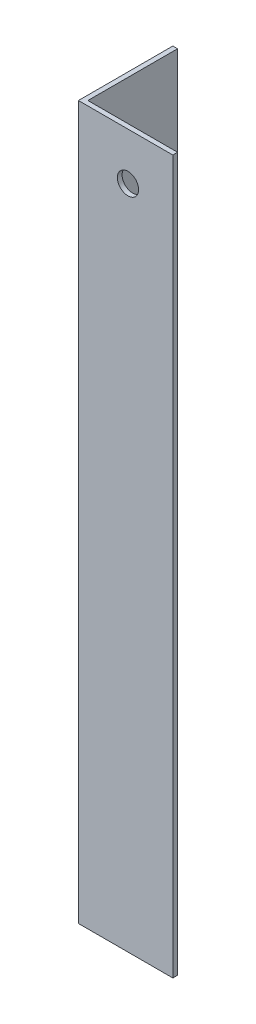
SolidWorks part; units mm, degrees
material "1060 Сплав"
ref_plane "Спереди" through (0, 0, 0) normal (0, 0, 1) x (1, 0, 0)
ref_plane "Сверху" through (0, 0, 0) normal (0, 1, 0) x (1, 0, 0)
ref_plane "Справа" through (0, 0, 0) normal (1, 0, 0) x (0, 0, -1)
sketch "Эскиз1" plane through (0, 0, 0) normal (0, 1, 0) x (1, 0, 0)
  line L0 (0, 0) -> (0, 20)
  line L1 (0, 20) -> (1, 20)
  line L2 (1, 20) -> (1, 1)
  line L3 (1, 1) -> (20, 1)
  line L4 (20, 1) -> (20, 0)
  line L5 (20, 0) -> (0, 0)
  dimension "D1" = 1
  dimension "D2" = 20
extrude "Бобышка-Вытянуть1" add sketch "Эскиз1" along normal blind 151
sketch "Эскиз2" plane through (0, 0, -1) normal (0, 0, -1) x (-1, 0, 0)
  line L0 (-10.5, 151) -> (-10.5, 141) construction
  line L1 (-20, 151) -> (-1, 151) construction
  circle A0 centre (-10.5, 141) radius 2.25
  dimension "D2" = 4.5
  dimension "D1" = 10
extrude "Вырез-Вытянуть1" cut sketch "Эскиз2" against normal through all
sketch "Эскиз3" plane through (1, 0, 0) normal (1, 0, 0) x (0, 0, -1)
  line L0 (10.5, 151) -> (10.5, 0) construction
  line L1 (1, 151) -> (20, 151) construction
  line L2 (1, 0) -> (20, 0) construction
  line L4 (115.0888, 20) -> (-26.9112, 20) construction
  line L5 (115.0888, 126) -> (-26.9112, 126) construction
  line L6 (115.0888, 126) -> (-26.9112, 126) construction
  line L8 (20, 151) -> (0, 151) construction
  line L9 (115.0888, 20) -> (-26.9112, 20) construction
  circle A0 centre (10.5, 116.5) radius 2.25
  circle A1 centre (10.5, 9.5) radius 2.25
  dimension "D1" = 34.5
  dimension "D2" = 4.5
  dimension "D3" = 9.5
  dimension "D4" = 4.5
extrude "Вырез-Вытянуть2" cut sketch "Эскиз3" against normal through all
